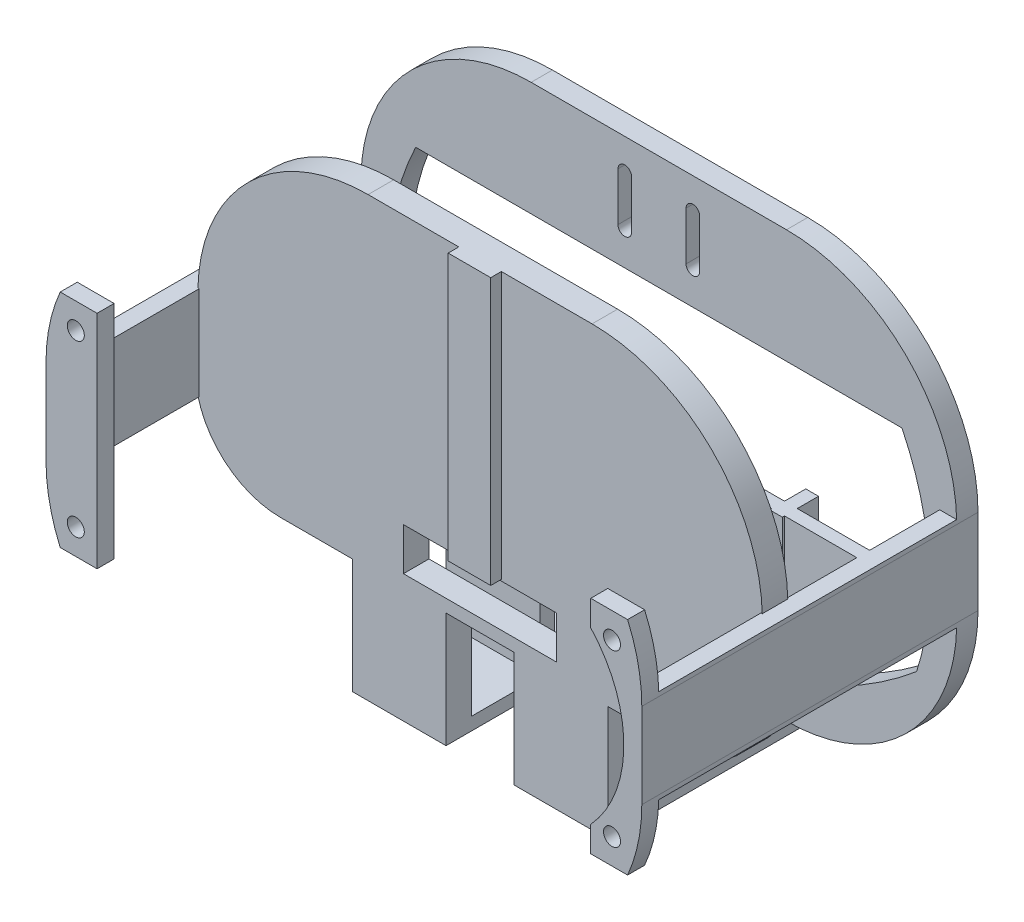
SolidWorks part; units mm, degrees
ref_plane "Front Plane" through (0, 0, 0) normal (0, 0, 1) x (1, 0, 0)
ref_plane "Top Plane" through (0, 0, 0) normal (0, 1, 0) x (1, 0, 0)
ref_plane "Right Plane" through (0, 0, 0) normal (1, 0, 0) x (0, 0, -1)
other "Center of Mass"
sketch "Sketch1" plane through (0, 0, 0) normal (0, 0, 1) x (1, 0, 0)
  line L1 (70, -50) -> (-70, -50)
  line L2 (70, -50) -> (70, 50)
  line L3 (70, 50) -> (-70, 50)
  line L4 (-70, -50) -> (-70, 50)
  line L5 (70, -50) -> (-70, 50) construction
  line L6 (70, 50) -> (-70, -50) construction
  point P0 (0, 0)
  dimension "D1" = 140
  dimension "D2" = 100
extrude "Boss-Extrude1" add sketch "Sketch1" along normal blind 5
sketch "Sketch2" plane through (0, 0, 5) normal (0, 0, 1) x (1, 0, 0)
  line L0 (-70, 0) -> (70, 0) construction
  line L1 (-70, 50) -> (-70, -50) construction
  line L2 (70, -50) -> (70, 50) construction
  line L3 (0, 50) -> (0, -50) construction
  line L4 (70, 50) -> (-70, 50) construction
  line L5 (-70, -50) -> (70, -50) construction
  line L6 (66, 26) -> (70, -26) construction
  line L7 (-66, -26) -> (-70, -26)
  line L8 (-66, -26) -> (-66, 26)
  line L9 (-66, 26) -> (-70, 26)
  line L10 (-70, -26) -> (-70, 26)
  line L11 (-66, -26) -> (-70, 26) construction
  line L12 (-66, 26) -> (-70, -26) construction
  line L13 (66, -26) -> (70, 26) construction
  line L14 (70, -26) -> (70, 26)
  line L15 (66, 26) -> (70, 26)
  line L16 (66, -26) -> (66, 26)
  line L17 (66, -26) -> (70, -26)
  point P12 (-68, 0)
  point P21 (68, 0)
  dimension "D1" = 4
  dimension "D2" = 0
  dimension "D3" = 52
extrude "Boss-Extrude2" add sketch "Sketch2" along normal blind 70
sketch "Sketch3" plane through (0, 0, 75) normal (0, 0, 1) x (1, 0, 0)
  line L0 (0, 50) -> (0, -50) construction
  line L1 (70, 50) -> (-70, 50) construction
  line L2 (-70, -50) -> (70, -50) construction
  line L4 (-70, 26) -> (-58, 26)
  line L5 (-70, 26) -> (-70, -26)
  line L6 (-70, -26) -> (-58, -26)
  line L7 (-58, 26) -> (-58, -26)
  line L8 (-70, -26) -> (-66, -26) construction
  line L9 (58, 26) -> (58, -26)
  line L10 (70, -26) -> (58, -26)
  line L11 (70, 26) -> (70, -26)
  line L12 (70, 26) -> (58, 26)
  dimension "D1" = 12
extrude "Boss-Extrude3" add sketch "Sketch3" along normal blind 4
sketch "Sketch4" plane through (0, 0, 79) normal (0, 0, 1) x (1, 0, 0)
  line L0 (-70, 0) -> (70, 0) construction
  line L1 (-70, 26) -> (-70, -26) construction
  line L2 (70, -26) -> (70, 26) construction
  line L3 (0, 50) -> (0, -50) construction
  line L4 (70, 50) -> (-70, 50) construction
  line L5 (-70, -50) -> (70, -50) construction
  circle A0 centre (-63, 20) radius 2
  circle A1 centre (-63, -20) radius 2
  circle A2 centre (63, 20) radius 2
  circle A3 centre (63, -20) radius 2
  dimension "D1" = 4
  dimension "D2" = 7
  dimension "D3" = 20
extrude "Cut-Extrude1" cut sketch "Sketch4" against normal blind 4
sketch "Sketch5" plane through (-70, 0, 0) normal (-1, 0, 0) x (0, 0, 1)
  line L0 (79, 26) -> (79, -26) construction
  line L1 (5, 26) -> (75, 26)
  line L2 (5, 26) -> (5, 11)
  line L3 (5, 11) -> (75, 11)
  line L4 (75, 26) -> (75, 11)
  line L5 (5, -26) -> (75, -26)
  line L6 (5, -26) -> (5, -11)
  line L7 (5, -11) -> (75, -11)
  line L8 (75, -26) -> (75, -11)
  dimension "D1" = 4
  dimension "D2" = 4
  dimension "D3" = 15
  dimension "D4" = 15
extrude "Cut-Extrude3" cut sketch "Sketch5" against normal through all
fillet "Fillet1" radius 40 4 edges at (70, -50, 2.5) (70, 50, 2.5) (-70, 50, 2.5) (-70, -50, 2.5)
sketch "Sketch9" plane through (0, 0, 0) normal (0, 0, -1) x (-1, 0, 0)
  line L0 (0, 50) -> (0, 23.9891) construction
  line L1 (-30, 50) -> (30, 50) construction
  line L2 (-8, 42.5954) -> (-8, 31.2501) construction
  line L3 (-6.4, 42.5954) -> (-6.4, 31.2501)
  line L4 (-9.6, 42.5954) -> (-9.6, 31.2501)
  line L5 (8, 42.5954) -> (8, 31.2501) construction
  line L6 (6.4, 42.5954) -> (6.4, 31.2501)
  line L7 (9.6, 42.5954) -> (9.6, 31.2501)
  arc A0 (-6.4, 42.5954) -> (-9.6, 42.5954) centre (-8, 42.5954) ccw
  arc A1 (-9.6, 31.2501) -> (-6.4, 31.2501) centre (-8, 31.2501) ccw
  arc A2 (6.4, 42.5954) -> (9.6, 42.5954) centre (8, 42.5954) cw
  arc A3 (9.6, 31.2501) -> (6.4, 31.2501) centre (8, 31.2501) cw
  point P7 (-8, 36.9227)
  point P14 (8, 36.9227)
  dimension "D2" = 1.6
  dimension "D1" = 8
extrude "Cut-Extrude6" cut sketch "Sketch9" against normal blind 10
sketch "Sketch11" plane through (0, -50, 0) normal (0, -1, 0) x (1, 0, 0)
  line L0 (0, 0) -> (0, 37.8621) construction
  line L1 (-30, 0) -> (-8, 0)
  line L2 (-30, 0) -> (-30, 41)
  line L3 (-30, 41) -> (-8, 41)
  line L4 (-8, 0) -> (-8, 41)
  line L6 (-30, 0) -> (30, 0) construction
  line L7 (8, 0) -> (8, 41)
  line L8 (30, 41) -> (8, 41)
  line L9 (30, 0) -> (30, 41)
  line L10 (30, 0) -> (8, 0)
  dimension "D1" = 22
  dimension "D2" = 41
extrude "Boss-Extrude6" add sketch "Sketch11" along normal blind 3
sketch "Sketch12" plane through (0, -53, 0) normal (0, -1, 0) x (1, 0, 0)
  line L0 (0, 60.22) -> (0, 0) construction
  line L1 (-30, 41) -> (-8, 41)
  line L2 (-30, 41) -> (-30, 47)
  line L3 (-30, 47) -> (-8, 47)
  line L4 (-8, 41) -> (-8, 47)
  line L5 (8, 41) -> (8, 47)
  line L6 (30, 47) -> (8, 47)
  line L7 (30, 41) -> (30, 47)
  line L8 (30, 41) -> (8, 41)
  dimension "D1" = 6
extrude "Boss-Extrude7" add sketch "Sketch12" against normal blind 30
sketch "Sketch15" plane through (0, 0, 47) normal (0, 0, 1) x (1, 0, 0)
  line L0 (-66.6606, -26) -> (-58, -26) construction
  line L1 (-66.3, -26) -> (66.3, -26)
  line L2 (-66.3, -26) -> (-66.3, 50)
  line L3 (-66.3, 50) -> (66.3, 50)
  line L4 (66.3, -26) -> (66.3, 50)
  line L7 (30, 50) -> (-30, 50) construction
  line L9 (70, -10) -> (70, 10) construction
  dimension "D1" = 0
  dimension "D2" = 0
  dimension "D3" = 3.7
  dimension "D4" = 3.7
extrude "Boss-Extrude8" add sketch "Sketch15" against normal blind 6
fillet "Fillet2" radius 40 2 edges at (66.3, 50, 44) (-66.3, 50, 44)
fillet "Fillet3" radius 20 2 edges at (66.3, -26, 44) (-66.3, -26, 44)
sketch "Sketch24" plane through (0, 0, 0) normal (0, 0, -1) x (-1, 0, 0)
  line L3 (57.1278, 23.2208) -> (-57.1278, 23.2208)
  line L5 (60.5793, -24.6237) -> (-57.1278, 23.2208) construction
  line L6 (57.1278, 23.2208) -> (-60.5793, -24.6237) construction
  arc A0 (-60.5793, -24.6237) -> (60.5793, -24.6237) centre (0, 47.1187) ccw
  arc A1 (-57.1278, 23.2208) -> (-60.5793, -24.6237) centre (0.6698, -4.9955) ccw
  arc A2 (57.1278, 23.2208) -> (60.5793, -24.6237) centre (-1.7816, -5.0757) cw
  point P0 (0, 0)
  point P9 (0, -46.7792)
  point P10 (-63.4808, -0.3677)
  point P11 (63.4019, -0.3733)
  dimension "D1" = 70
  dimension "D2" = 126.8828
extrude "Cut-Extrude13" cut sketch "Sketch24" against normal blind 10
sketch "Sketch25" plane through (0, 0, 47) normal (0, 0, 1) x (1, 0, 0)
  line L0 (0, 50) -> (0, -26) construction
  line L1 (26.3125, 50) -> (-26.3125, 50) construction
  line L2 (-8, -26) -> (8, -26) construction
  line L4 (-5, 50) -> (5, 50)
  line L5 (-5, 50) -> (-5, -12.6486)
  line L6 (-5, -12.6486) -> (5, -12.6486)
  line L7 (5, 50) -> (5, -12.6486)
  dimension "D1" = 5
  dimension "D2" = 5
extrude "Boss-Extrude9" add sketch "Sketch25" along normal blind 2.5
sketch "Sketch26" plane through (0, 0, 41) normal (0, 0, -1) x (-1, 0, 0)
  line L0 (0, 50) -> (0, -26) construction
  line L2 (-66, -11) -> (-66, 11)
  line L4 (66.3, -11) -> (66.3, 11)
  line L5 (-26.3125, 50) -> (26.3125, 50) construction
  line L6 (8, -26) -> (-8, -26) construction
  line L7 (-10.75, -11) -> (-10.75, -13)
  line L9 (10.75, -11) -> (10.75, 11)
  line L11 (-10.75, -11) -> (-10.75, 11)
  line L12 (10.75, -11) -> (-10.75, 11) construction
  line L13 (10.75, 11) -> (-10.75, -11) construction
  line L14 (13, -13) -> (10.75, -13)
  line L15 (13, -13) -> (13, 13)
  line L16 (13, 13) -> (10.75, 13)
  line L17 (-13, -13) -> (-13, 13)
  line L18 (13, -13) -> (-11.184, 11.184) construction
  line L19 (10.702, 10.702) -> (-13, -13) construction
  line L20 (-10.75, -13) -> (-10.75, 13)
  line L21 (10.75, 13) -> (10.75, -13)
  line L22 (-10.75, 13) -> (-13, 13)
  line L25 (-10.75, -13) -> (-13, -13)
  point P12 (0, 0)
  point P18 (0, 0)
  dimension "D1" = 21.5
  dimension "D2" = 22
  dimension "D3" = 26
  dimension "D4" = 26
  dimension "D5" = 10.75
extrude "Boss-Extrude10" add sketch "Sketch26" along normal blind 16 contours L25 L7 L11 L20 L22 L17 | L16 L21 L9 L14 L15 region at (11.875, 0, 41) region at (-11.875, 0, 41)
sketch "Sketch27" plane through (0, 13, 0) normal (0, 1, 0) x (1, 0, 0)
  line L0 (-10.75, -25) -> (-10.75, -41) construction
  line L1 (-10.75, -36) -> (10.75, -36)
  line L2 (-10.75, -36) -> (-10.75, -33.5)
  line L3 (-10.75, -33.5) -> (10.75, -33.5)
  line L4 (10.75, -36) -> (10.75, -33.5)
  line L5 (10.75, -25) -> (10.75, -41) construction
  line L6 (26.3125, -41) -> (-26.3125, -41) construction
  line L7 (-13, -25) -> (-10.75, -25) construction
  dimension "D1" = 5
  dimension "D2" = 2.5
  dimension "D3" = 8.5
extrude "Boss-Extrude11" add sketch "Sketch27" against normal blind 26
fillet "Fillet4" radius 5 2 edges at (13, 0, 41) (-13, 0, 41)
sketch "Sketch29" plane through (0, 0, 33.5) normal (0, 0, -1) x (-1, 0, 0)
  line L0 (-10.75, -13) -> (10.75, -13) construction
  line L1 (-10.75, -3) -> (3.25, -3)
  line L2 (-10.75, -3) -> (-10.75, -13)
  line L3 (-10.75, -13) -> (3.25, -13)
  line L4 (3.25, -3) -> (3.25, -13)
  line L5 (-10.75, -13) -> (-10.75, 13) construction
  dimension "D1" = 14
  dimension "D2" = 0
  dimension "D3" = 10
  dimension "D4" = 0
extrude "Cut-Extrude14" cut sketch "Sketch29" against normal blind 5
sketch "Sketch30" plane through (0, 0, 75) normal (0, 0, -1) x (-1, 0, 0)
  line L0 (-58, 26) -> (-58, -26) construction
  line L1 (-58, 20) -> (-58, -20)
  arc A0 (-58, 20) -> (-58, -20) centre (-36.1952, 0) ccw
extrude "Cut-Extrude15" cut sketch "Sketch30" against normal blind 5
sketch "Sketch33" plane through (0, 11, 0) normal (0, 1, 0) x (1, 0, 0)
  line L0 (-66, -5) -> (-66, -41) construction
  line L1 (-66, -25) -> (-30, -25)
  line L2 (-66, -25) -> (-66, -22)
  line L3 (-66, -22) -> (-30, -22)
  line L4 (-30, -25) -> (-30, -22)
  line L5 (66, -41) -> (66, -5) construction
  line L6 (66, -24.4737) -> (30, -24.4737)
  line L7 (66, -24.4737) -> (66, -21.4737)
  line L8 (66, -21.4737) -> (30, -21.4737)
  line L9 (30, -24.4737) -> (30, -21.4737)
  line L10 (-69.9875, -5) -> (-30, -5) construction
  dimension "D1" = 3
  dimension "D2" = 3
  dimension "D3" = 36
  dimension "D4" = 36
  dimension "D5" = 17
extrude "Boss-Extrude12" add sketch "Sketch33" against normal blind 22
sketch "Sketch34" plane through (0, 0, 21.4737) normal (0, 0, -1) x (-1, 0, 0)
  line L0 (-66, 11) -> (-30, 11) construction
  line L1 (46, -36) -> (-46, -36)
  line L2 (46, -36) -> (46, 36)
  line L3 (46, 36) -> (-46, 36)
  line L4 (-46, -36) -> (-46, 36)
  line L5 (46, -36) -> (-46, 36) construction
  line L6 (46, 36) -> (-46, -36) construction
  line L7 (-46, -11) -> (-49, -11)
  line L8 (-46, -11) -> (-46, 11)
  line L9 (-46, 11) -> (-49, 11)
  line L10 (-49, -11) -> (-49, 11)
  line L11 (30, 11) -> (66, 11) construction
  line L12 (46, 11) -> (49, 11)
  line L13 (46, 11) -> (46, -11)
  line L14 (46, -11) -> (49, -11)
  line L15 (49, 11) -> (49, -11)
  line L16 (30, -11) -> (66, -11) construction
  line L19 (-8, -26) -> (-8, -50) construction
  line L20 (-30, -50) -> (-8, -50)
  line L21 (-30, -50) -> (-30, -33)
  line L22 (-30, -33) -> (-8, -33)
  line L23 (-8, -50) -> (-8, -33)
  line L24 (30, -26) -> (30, -50) construction
  line L25 (8, -50) -> (30, -50)
  line L26 (8, -50) -> (8, -33)
  line L27 (8, -33) -> (30, -33)
  line L28 (30, -50) -> (30, -33)
  point P0 (0, 0)
  line M10 (-30, 11) -> (-66, 11)
  line M12 (-66, -11) -> (-30, -11)
  dimension "D1" = 92
  dimension "D2" = 72
  dimension "D3" = 3
  dimension "D4" = 3
  dimension "D5" = 0
  dimension "D6" = 22
  dimension "D7" = 17
  dimension "D8" = 17
extrude "Boss-Extrude13" add sketch "Sketch34" along normal blind 5 and the other way blind 3.5 contours L10 L4 M12 M10 | L15 L14 L13 L12 | L8 L7 L10 L9 | L21 L20 L23 L22 | L26 L25 L28 L27 region at (47.5, 0, 21.4737)
sketch "Sketch35" plane through (-30, 0, 0) normal (-1, 0, 0) x (0, 0, 1)
  line L0 (47, -53) -> (0, -53) construction
  line L1 (16.4737, -33) -> (21.4737, -33)
  line L2 (16.4737, -33) -> (16.4737, -50)
  line L3 (16.4737, -50) -> (21.4737, -50)
  line L4 (21.4737, -33) -> (21.4737, -50)
  line L6 (21.4737, -11) -> (21.4737, 11) construction
  dimension "D1" = 3
  dimension "D2" = 0
extrude "Cut-Extrude16" cut sketch "Sketch35" against normal through all
sketch "Sketch36" plane through (0, 0, 41) normal (0, 0, -1) x (-1, 0, 0)
  line L1 (-18, -13) -> (18.012, -13)
  line L2 (-18, -13) -> (-18, -23)
  line L3 (-18, -23) -> (18.012, -23)
  line L4 (18.012, -13) -> (18.012, -23)
  dimension "D1" = 10
extrude "Cut-Extrude17" cut sketch "Sketch36" against normal blind 8
